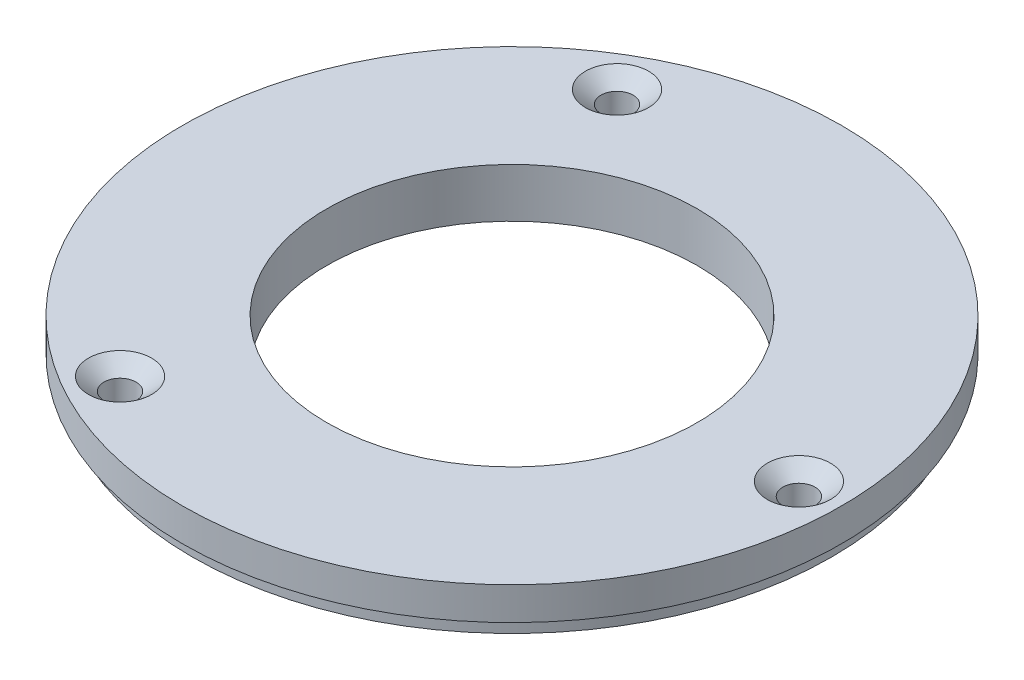
SolidWorks part; units mm, degrees
material "6061-T6 (SS)"
ref_plane "Front Plane" through (0, 0, 0) normal (0, 0, 1) x (1, 0, 0)
ref_plane "Top Plane" through (0, 0, 0) normal (0, 1, 0) x (1, 0, 0)
ref_plane "Right Plane" through (0, 0, 0) normal (1, 0, 0) x (0, 0, -1)
sketch "Sketch1" plane through (0, 0, 0) normal (0, 1, 0) x (1, 0, 0)
  circle A0 centre (0, 0) radius 51.054
  circle A1 centre (0, 0) radius 28.702
  dimension "D1" = 57.404
  dimension "D2" = 102.108
extrude "Boss-Extrude1" add sketch "Sketch1" along normal blind 7.62
hole_wizard "CSK for #10 Flat Head Machine Screw (100)1" positions "Sketch4" profile "Sketch5" countersink size "#10" standard "ANSI Inch" end condition through all
sketch "Sketch4" plane through (0, 7.62, 0) normal (0, 1, 0) x (1, 0, 0)
  line L0 (-65.4508, 0) -> (95.8403, 0) construction
  point P0 (44.45, 0)
  dimension "D1" = 44.45
sketch "Sketch5" plane through (44.45, 7.62, 0) normal (1, 0, 0) x (0, 0, 1)
  line L0 (0, 0) -> (0, 7.62)
  line L1 (0, 7.62) -> (2.4892, 7.62)
  line L2 (2.4892, 7.62) -> (2.4892, 2.0141)
  line L3 (2.4892, 2.0141) -> (4.8895, 0)
  line L5 (4.8895, 0) -> (0, 0)
  line L6 (-2.4892, 2.0141) -> (-4.8895, 0) construction
  line L11 (0, -6.35) -> (0, 107.95) construction
  dimension "Thru Hole Dia." = 4.9784
  dimension "Thru Hole Depth" = 7.62
  dimension "Near C'Sink Dia." = 9.779
  dimension "Near C'Sink Angle" = 100
pattern_circular "CirPattern1" count 4 every 120 about axis through (0, 7.62, 0) along (0, 1, 0) of "CSK for #10 Flat Head Machine Screw (100)1"
sketch "Sketch6" plane through (0, 0, 0) normal (0, -1, 0) x (1, 0, 0)
  circle A0 centre (0, 0) radius 49.53
  circle A1 centre (0, 0) radius 51.054
  dimension "D2" = 102.108
  dimension "D1" = 99.06
extrude "Cut-Extrude1" cut sketch "Sketch6" against normal blind 2.54
equation "\"ID\"= 2.26in"
equation "\"D1@Sketch1\"=\"ID\""
equation "\"OD\"= 4.02in"
equation "\"h\"= 0.3"
equation "\"D1@Boss-Extrude1\"=\"h\""
equation "\"HoleDist\"=1.75"
equation "\"D1@Sketch4\"=\"HoleDist\""
equation "\"D2@Sketch1\"=\"OD\""
equation "\"CouplerDia\"= 3.9"
equation "\"D1@Sketch6\"=\"CouplerDia\""
equation "\"D2@Sketch6\"=\"OD\""
